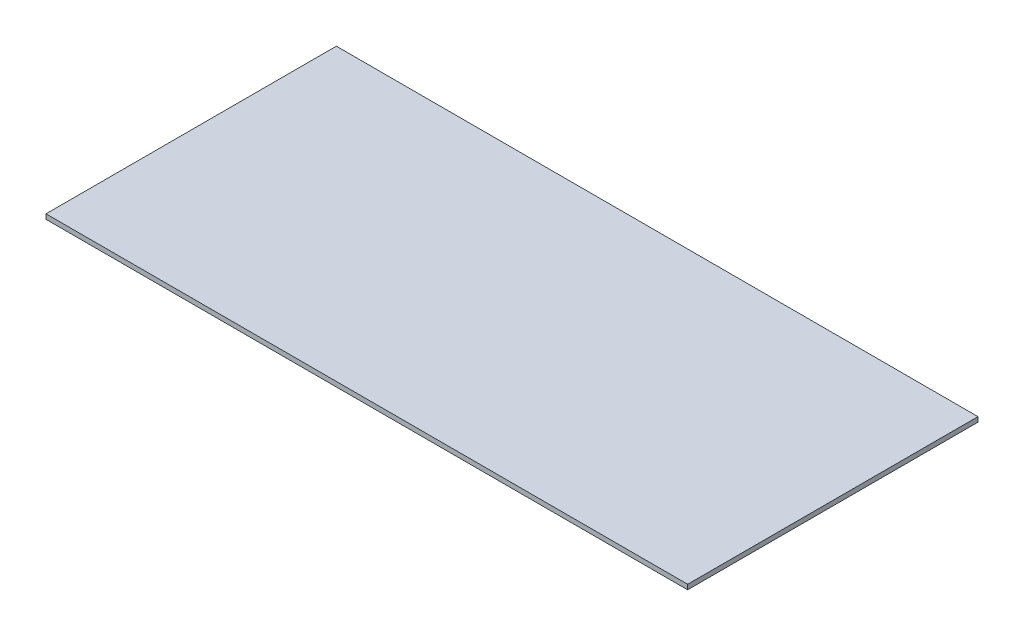
SolidWorks part; units mm, degrees
ref_plane "Front Plane" through (0, 0, 0) normal (0, 0, 1) x (1, 0, 0)
ref_plane "Top Plane" through (0, 0, 0) normal (0, 1, 0) x (1, 0, 0)
ref_plane "Right Plane" through (0, 0, 0) normal (1, 0, 0) x (0, 0, -1)
sketch "Sketch1" plane through (0, 0, 0) normal (0, 1, 0) x (1, 0, 0)
  line L1 (0, 0) -> (400, 0)
  line L2 (0, 0) -> (0, 181)
  line L3 (0, 181) -> (400, 181)
  line L4 (400, 0) -> (400, 181)
  dimension "D1" = 181
  dimension "D2" = 400
extrude "Boss-Extrude1" add sketch "Sketch1" along normal blind 3
